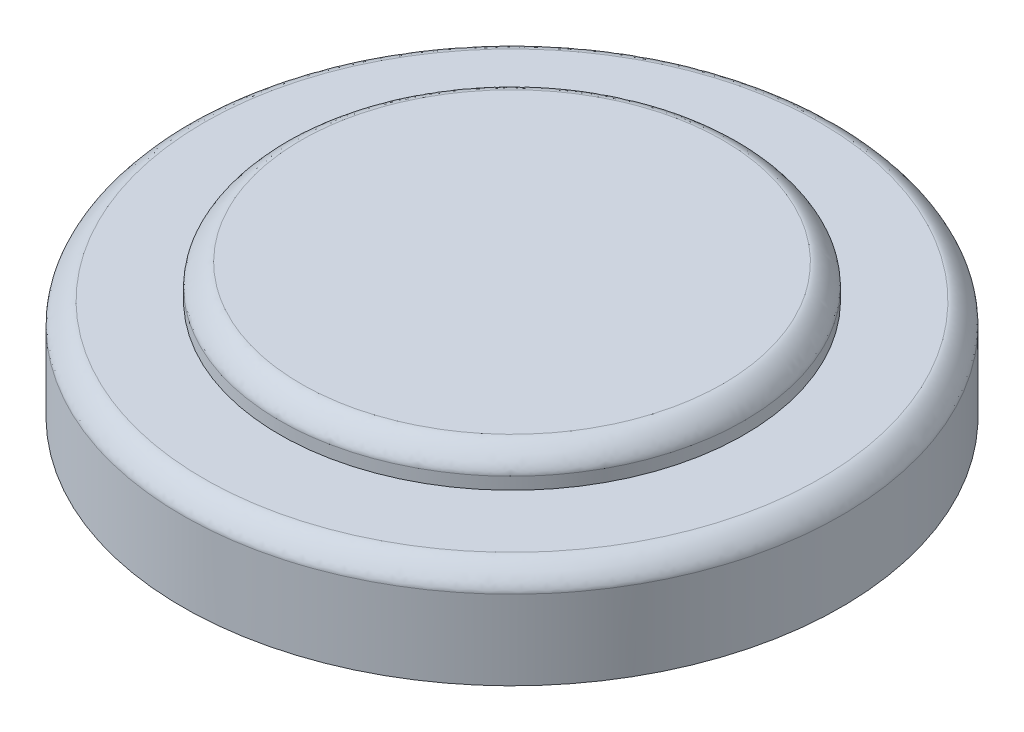
SolidWorks part; units mm, degrees
material "Stainless Steel (ferritic)"
ref_plane "Front Plane" through (0, 0, 0) normal (0, 0, 1) x (1, 0, 0)
ref_plane "Top Plane" through (0, 0, 0) normal (0, 1, 0) x (1, 0, 0)
ref_plane "Right Plane" through (0, 0, 0) normal (1, 0, 0) x (0, 0, -1)
sketch "Sketch1" plane through (0, 0, 0) normal (0, 0, 1) x (1, 0, 0)
  line L0 (0, 0) -> (0, 76.2) construction
  line L23 (25.7039, 0) -> (39.3517, 0)
  line L24 (39.3517, 0) -> (39.3517, 12.0138)
  line L25 (39.3517, 12.0138) -> (27.7376, 12.0138)
  line L26 (27.7376, 12.0138) -> (27.7376, 16.0058)
  line L27 (27.7376, 16.0058) -> (0, 16.0058)
  line L28 (0, 16.0058) -> (0, 12.0138)
  line L29 (0, 12.0138) -> (25.7039, 12.0138)
  line L30 (25.7039, 12.0138) -> (25.7039, 0)
revolve "Revolve1" add sketch "Sketch1" angle 360 about L0
fillet "Fillet1" radius 2.54 3 edges at (0, 12.0138, -39.3517) (0, 16.0058, -27.7376) (0, 12.0138, -25.7039) conic radius 4.92
